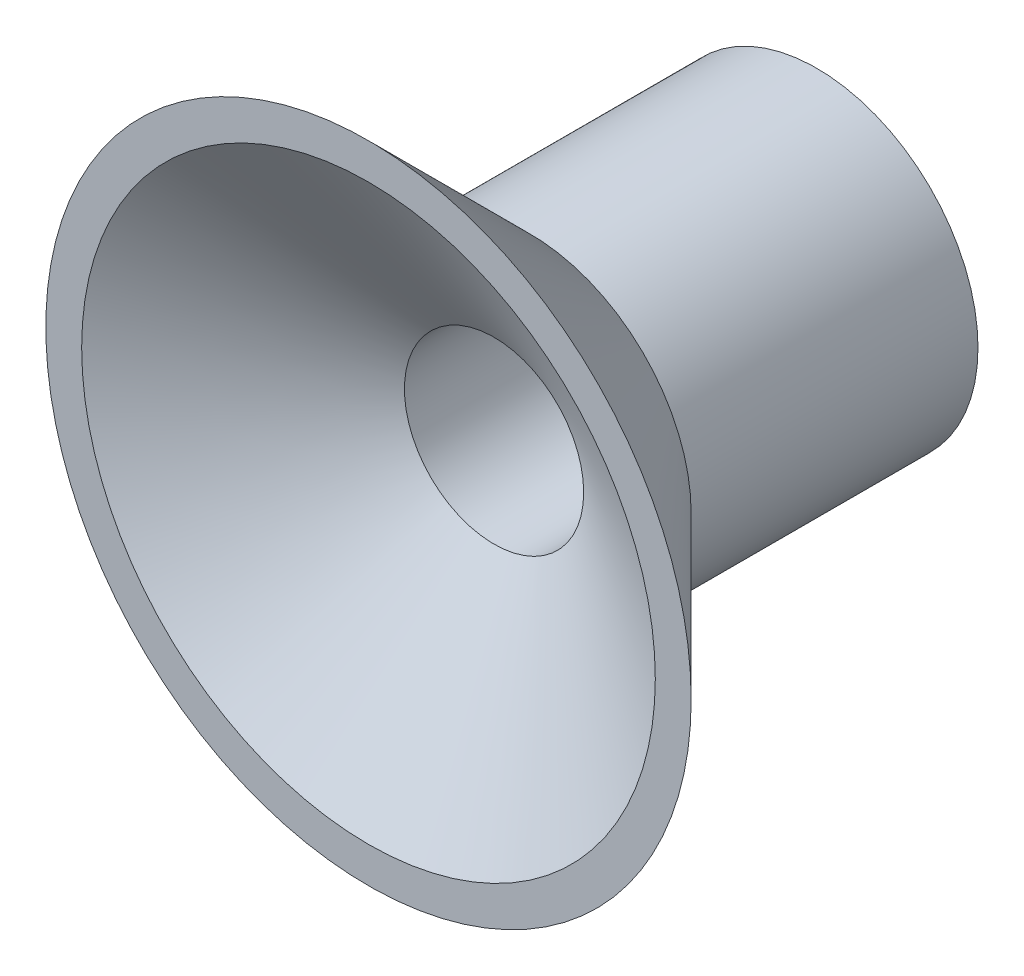
SolidWorks part; units mm, degrees
material "硅橡胶"
ref_plane "前视基准面" through (0, 0, 0) normal (0, 0, 1) x (1, 0, 0)
ref_plane "上视基准面" through (0, 0, 0) normal (0, 1, 0) x (1, 0, 0)
ref_plane "右视基准面" through (0, 0, 0) normal (1, 0, 0) x (0, 0, -1)
sketch "草图1" plane through (0, 0, 0) normal (0, 1, 0) x (1, 0, 0)
  line L0 (0, 0) -> (0, 42.6689) construction
  line L1 (-2.5, 12.5) -> (-2.5, 3.5023)
  line L2 (-8, 0) -> (-9, 0)
  line L4 (-2.5, 12.5) -> (-4.5, 12.5)
  line L5 (-2.5, 3.5023) -> (-8, 0)
  line L7 (-4.5, 12.5) -> (-4.5, 4.5)
  line L8 (-4.5, 4.5) -> (-9, 0)
  dimension "D1" = 8
  dimension "D2" = 1
  dimension "D3" = 2
  dimension "D4" = 2.5
revolve "旋转1" add sketch "草图1" angle 360 about L0
